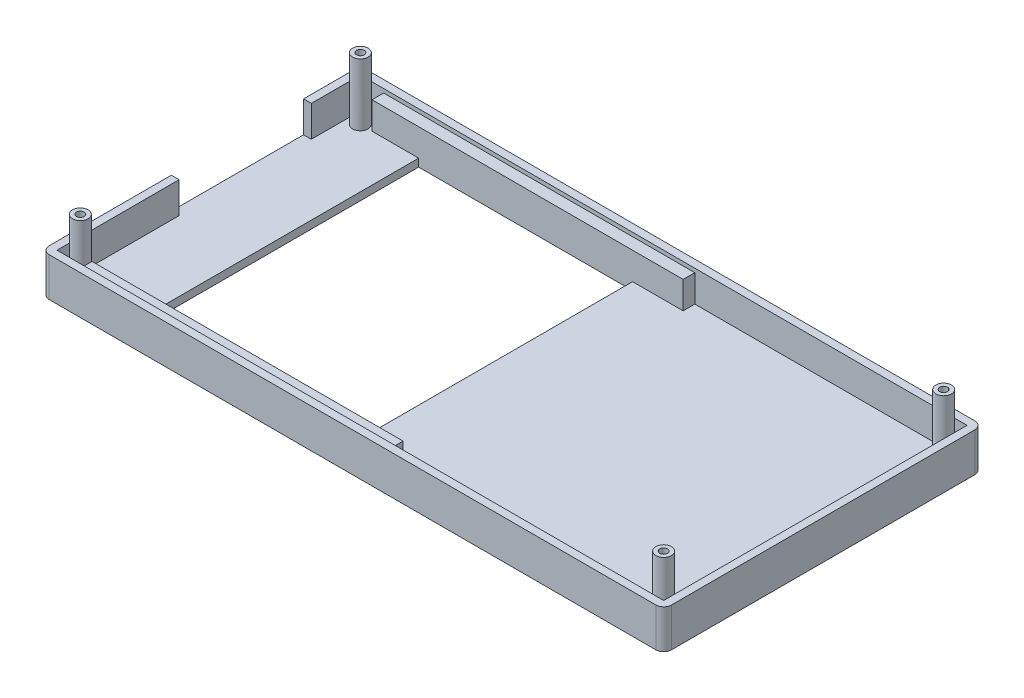
SolidWorks part; units mm, degrees
ref_plane "Front Plane" through (0, 0, 0) normal (0, 0, 1) x (1, 0, 0)
ref_plane "Top Plane" through (0, 0, 0) normal (0, 1, 0) x (1, 0, 0)
ref_plane "Right Plane" through (0, 0, 0) normal (1, 0, 0) x (0, 0, -1)
sketch "Sketch1" plane through (0, 0, 0) normal (0, 1, 0) x (1, 0, 0)
  line L1 (-80, -41) -> (80, -41)
  line L2 (-80, -41) -> (-80, 41)
  line L3 (-80, 41) -> (80, 41)
  line L4 (80, -41) -> (80, 41)
  line L5 (-80, -41) -> (80, 41) construction
  line L6 (-80, 41) -> (80, -41) construction
  point P0 (0, 0)
  dimension "D1" = 160
  dimension "D2" = 82
extrude "Boss-Extrude1" add sketch "Sketch1" along normal blind 10 contours L1 L4 L3 L2
shell "Shell1" thickness 2 removed face at (0, 10, 0)
sketch "Sketch2" plane through (0, 2, 0) normal (0, 1, 0) x (1, 0, 0)
  line L0 (-78, 39) -> (78, 39) construction
  line L1 (-78, -39) -> (-78, 39) construction
  line L2 (0, 39) -> (0, -41) construction
  line L3 (-78, 39) -> (78, 39) construction
  line L4 (-80, -41) -> (80, -41) construction
  line L5 (-80, 0) -> (80, 0) construction
  line L6 (-80, -41) -> (-80, 41) construction
  line L7 (80, -41) -> (80, 41) construction
  circle A0 centre (-75, 36) radius 1
  circle A1 centre (75, 36) radius 1
  circle A2 centre (75, -36) radius 1
  circle A3 centre (-75, -36) radius 1
  circle A4 centre (-75, 36) radius 2
  circle A5 centre (75, 36) radius 2
  circle A6 centre (-75, -36) radius 2
  circle A7 centre (75, -36) radius 2
  dimension "D1" = 3
  dimension "D2" = 3
  dimension "D3" = 2
  dimension "D4" = 1
fillet "Fillet1" radius 2 1 edges at (-80, 5, 41)
fillet "Fillet2" radius 2 1 edges at (-80, 5, -41)
fillet "Fillet3" radius 2 1 edges at (80, 5, -41)
fillet "Fillet4" radius 2 1 edges at (80, 5, 41)
sketch "Sketch10" plane through (-80, 0, 0) normal (-1, 0, 0) x (0, 0, 1)
  line L0 (7.6, 0) -> (-26.4, 0)
  line L1 (-41, 0) -> (-41, 10) construction
  line L2 (39, 0) -> (-39, 0) construction
  line L3 (-26.4, 0) -> (-26.4, 2)
  line L4 (-26.4, 2) -> (7.6, 2)
  line L5 (-26.4, 2) -> (7.6, 2)
  line L6 (-26.4, 2) -> (-26.4, 10.0297)
  line L7 (7.6, 2) -> (7.6, 10.0297)
  line L8 (-26.4, 10.0297) -> (7.6, 10.0297)
  dimension "D1" = 34
  dimension "D2" = 14.6
  dimension "D3" = 2
extrude "Cut-Extrude1" cut sketch "Sketch10" against normal blind 6 contours L4 L7 L8 L6
extrude "Boss-Extrude7" add sketch "Sketch2" along normal blind 16 contours A0 | A3 | A6 | A2 | A7 | A5 | A1 | A4
sketch "Sketch12" plane through (0, 2, 0) normal (0, 1, 0) x (1, 0, 0)
  line L0 (-55.169, 27.9209) -> (-55.169, 31.6209)
  line L1 (-55.169, -20.9591) -> (-55.169, -24.6591)
  line L2 (2.731, -20.9591) -> (2.731, -24.6591)
  line L3 (2.731, 27.9209) -> (2.731, 31.6209)
  line L4 (-78, -39) -> (-78, -7.6) construction
  line L5 (-72, 39) -> (8, 39)
  line L6 (-72, 39) -> (-72, 36)
  line L7 (-72, 36) -> (8, 36)
  line L8 (8, 39) -> (8, 36)
  line L9 (71.831, 0) -> (-89.6429, 0) construction
  line L11 (8, -39) -> (8, -36)
  line L12 (-72, -39) -> (8, -39)
  line L13 (-72, -39) -> (-72, -36)
  line L14 (-72, -36) -> (8, -36)
  line L15 (-78, -39) -> (78, -39) construction
  line L16 (-78, 39) -> (78, 39) construction
  dimension "D1" = 3.7
  dimension "D2" = 3.7
  dimension "D3" = 3
  dimension "D4" = 80
  dimension "D5" = 0
  dimension "D6" = 0
  dimension "D7" = 6
extrude "Boss-Extrude8" add sketch "Sketch12" along normal blind 7 contours L6 L7 L8 L5 | L14 L11 L12 L13
sketch "Sketch13" plane through (0, 2, 0) normal (0, 1, 0) x (1, 0, 0)
  line L1 (-60, 36) -> (-5, 36)
  line L2 (-60, 36) -> (-60, -36)
  line L3 (-60, -36) -> (-5, -36)
  line L4 (-5, 36) -> (-5, -36)
  line L5 (-78, -39) -> (78, -39) construction
  line L6 (-78, 26.4) -> (-78, 39) construction
  dimension "D1" = 72
  dimension "D2" = 3
  dimension "D3" = 55
  dimension "D4" = 18
extrude "Cut-Extrude3" cut sketch "Sketch13" against normal blind 200 contours L1 L4 L3 L2
